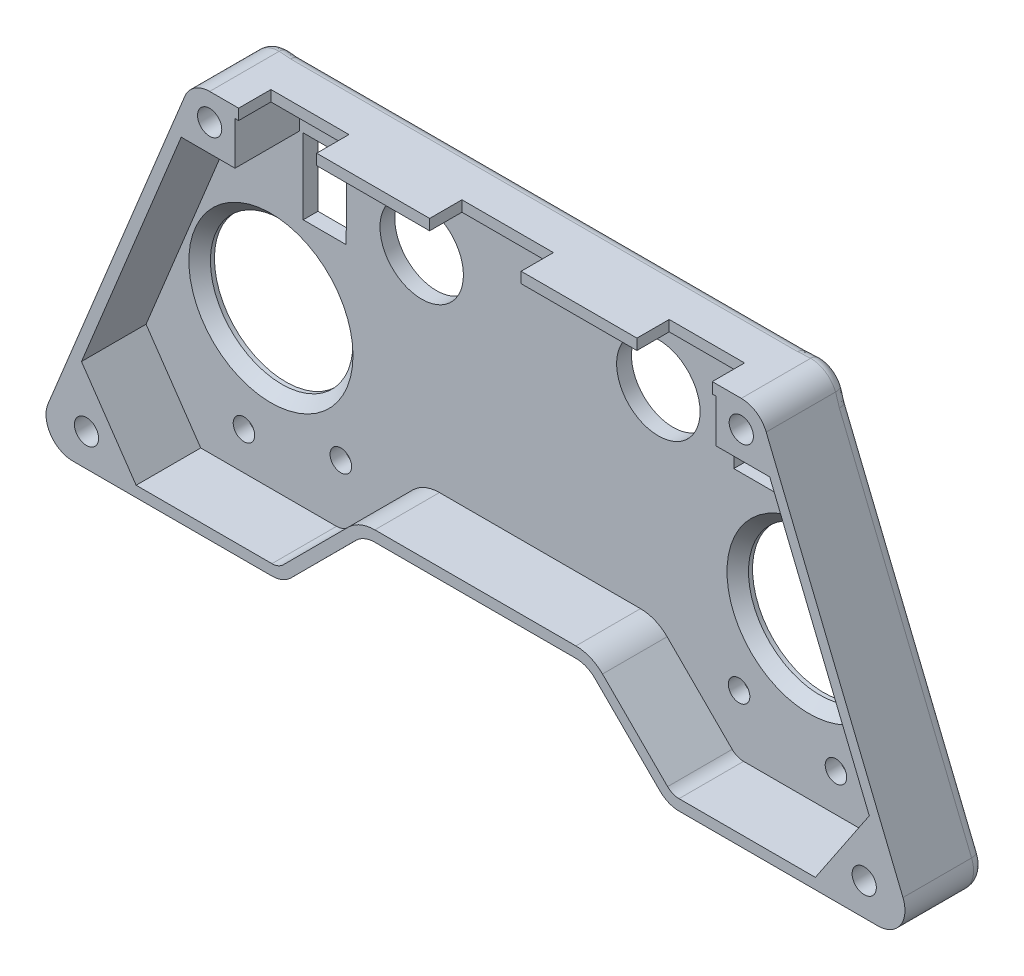
SolidWorks part; units mm, degrees
ref_plane "Plan de face" through (0, 0, 0) normal (0, 0, 1) x (1, 0, 0)
ref_plane "Plan de dessus" through (0, 0, 0) normal (0, 1, 0) x (1, 0, 0)
ref_plane "Plan de droite" through (0, 0, 0) normal (1, 0, 0) x (0, 0, -1)
sketch "Esquisse1" plane through (0, 0, 0) normal (0, 0, 1) x (1, 0, 0)
  line L8 (18.6789, 0) -> (-18.6789, 0)
  line L9 (-22.2167, -1.4667) -> (-34.2683, -13.5333)
  line L10 (-37.806, -15) -> (-74.7892, -15)
  line L11 (22.2123, -1.4623) -> (34.3028, -13.5377)
  line L12 (37.8361, -15) -> (74.8229, -15)
  line L13 (-79.4178, -8.109) -> (-54.0033, 54.0973)
  line L14 (-49.3747, 57.2063) -> (49.4084, 57.2063)
  line L15 (54.037, 54.0973) -> (79.4515, -8.109)
  line L16 (0.0169, 57.2063) -> (0, 0) construction
  arc A0 (-34.2683, -13.5333) -> (-37.806, -15) centre (-37.806, -10) cw
  arc A1 (-18.6789, 0) -> (-22.2167, -1.4667) centre (-18.6789, -5) ccw
  arc A2 (22.2123, -1.4623) -> (18.6789, 0) centre (18.6789, -5) ccw
  arc A3 (37.8361, -15) -> (34.3028, -13.5377) centre (37.8361, -10) cw
  arc A4 (54.037, 54.0973) -> (49.4084, 57.2063) centre (49.4084, 52.2063) ccw
  arc A5 (-49.3747, 57.2063) -> (-54.0033, 54.0973) centre (-49.3747, 52.2063) ccw
  arc A6 (79.4515, -8.109) -> (74.8229, -15) centre (74.8229, -10) cw
  arc A7 (-79.4178, -8.109) -> (-74.7892, -15) centre (-74.7892, -10) ccw
  point P4 (0, 0)
  point P12 (-35.7331, -15)
  point P15 (-20.7518, 0)
  point P18 (20.7482, 0)
  point P21 (35.7669, -15)
  point P24 (52.7669, 57.2063)
  point P27 (-52.7331, 57.2063)
  point P30 (82.2669, -15)
  point P33 (-82.2331, -15)
  dimension "D10" = 5
  dimension "D1" = 46.5
  dimension "D2" = 46.5
  dimension "D3" = 41.5
  dimension "D4" = 15
  dimension "D5" = 15
  dimension "D6" = 21.2
  dimension "D7" = 78
  dimension "D8" = 78
  dimension "D9" = 105.5
extrude "Boss.-Extru.1" add sketch "Esquisse1" along normal blind 14.75
sketch "Sketch1" plane through (0, 0, 0) normal (0, 0, 1) x (1, 0, 0)
  line L0 (37.8361, -15) -> (74.8229, -15) construction
  line L1 (49.4084, 57.2063) -> (-49.3747, 57.2063) construction
  line L2 (44.0169, 47.2063) -> (36.0169, 47.2063)
  line L3 (44.0169, 47.2063) -> (44.0169, 33.2063)
  line L4 (44.0169, 33.2063) -> (36.0169, 33.2063)
  line L5 (36.0169, 47.2063) -> (36.0169, 33.2063)
  line L6 (0.0169, 57.2063) -> (0, 0) construction
  line L7 (-18.6789, 0) -> (18.6789, 0) construction
  line L8 (-43.9973, 33.2322) -> (-35.9973, 33.2275)
  line L9 (-35.989, 47.2275) -> (-35.9973, 33.2275)
  line L10 (-43.989, 47.2322) -> (-35.989, 47.2275)
  line L11 (-43.989, 47.2322) -> (-43.9973, 33.2322)
  circle A0 centre (50, 16) radius 13.25
  circle A1 centre (22, 39.2063) radius 7.75
  circle A2 centre (-49.9906, 16.0295) radius 13.25
  circle A3 centre (-21.9769, 39.2193) radius 7.75
  point P11 (0.0169, 57.2063)
  dimension "D1" = 26.5
  dimension "D2" = 31
  dimension "D3" = 50
  dimension "D7" = 15.5
  dimension "D8" = 22
  dimension "D10" = 18
  dimension "D4" = 8
  dimension "D5" = 14
  dimension "D6" = 36
  dimension "D9" = 10
extrude "Cut-Extrude4" cut sketch "Sketch1" along normal blind 40 contours A0 | L3 L2 L5 L4 | A1 | A3 | L8 L9 L10 L11 | A2
sketch "Sketch3" plane through (0, 0, 14.75) normal (0, 0, 1) x (1, 0, 0)
  line L0 (-54.6596, 47.2027) -> (-73.1968, 1.8299)
  line L1 (44.6919, 55.2063) -> (-44.6596, 55.2063)
  line L2 (54.6919, 47.2063) -> (73.1932, 1.9213)
  line L3 (49.4084, 57.2063) -> (-49.3747, 57.2063) construction
  line L7 (-54.0033, 54.0973) -> (-79.4178, -8.109) construction
  line L8 (79.4515, -8.109) -> (54.037, 54.0973) construction
  line L72 (-73.1968, 1.8299) -> (-63.0357, -13)
  line L74 (-37.806, -13) -> (-63.0357, -13)
  line L75 (63.1707, -13) -> (73.1932, 1.9213)
  line L76 (37.8361, -13) -> (63.1707, -13)
  line L78 (-54.6596, 47.2027) -> (-44.6596, 47.2027)
  line L79 (-44.6596, 47.2027) -> (-44.6596, 55.2063)
  line L80 (77.6001, -8.8654) -> (52.1856, 53.3409)
  line L81 (37.8361, -13) -> (74.8229, -13)
  line L82 (23.6256, -0.0472) -> (35.7161, -12.1226)
  line L83 (-18.6789, 2) -> (18.6789, 2)
  line L84 (-35.6834, -12.12) -> (-23.6318, -0.0533)
  line L85 (-74.7892, -13) -> (-37.806, -13)
  line L86 (-52.1519, 53.3409) -> (-77.5664, -8.8654)
  line L87 (49.4084, 55.2063) -> (-49.3747, 55.2063)
  line L90 (23.6256, -0.0472) -> (35.7161, -12.1226)
  line L91 (-18.6789, 2) -> (18.6789, 2)
  line L92 (-35.6834, -12.12) -> (-23.6318, -0.0533)
  line L96 (44.6919, 55.2063) -> (44.6919, 47.2063)
  line L97 (44.6919, 47.2063) -> (54.6919, 47.2063)
  arc A0 (-79.4178, -8.109) -> (-74.7892, -15) centre (-74.7892, -10) ccw construction
  arc A1 (74.8229, -15) -> (79.4515, -8.109) centre (74.8229, -10) ccw construction
  arc A72 (52.1856, 53.3409) -> (49.4084, 55.2063) centre (49.4084, 52.2063) ccw
  arc A73 (74.8229, -13) -> (77.6001, -8.8654) centre (74.8229, -10) ccw
  arc A74 (35.7161, -12.1226) -> (37.8361, -13) centre (37.8361, -10) ccw
  arc A75 (23.6256, -0.0472) -> (18.6789, 2) centre (18.6789, -5) ccw
  arc A76 (-18.6789, 2) -> (-23.6318, -0.0533) centre (-18.6789, -5) ccw
  arc A77 (-37.806, -13) -> (-35.6834, -12.12) centre (-37.806, -10) ccw
  arc A78 (-77.5664, -8.8654) -> (-74.7892, -13) centre (-74.7892, -10) ccw
  arc A79 (-49.3747, 55.2063) -> (-52.1519, 53.3409) centre (-49.3747, 52.2063) ccw
  arc A82 (35.7161, -12.1226) -> (37.8361, -13) centre (37.8361, -10) ccw
  arc A83 (23.6256, -0.0472) -> (18.6789, 2) centre (18.6789, -5) ccw
  arc A84 (-18.6789, 2) -> (-23.6318, -0.0533) centre (-18.6789, -5) ccw
  arc A85 (-37.806, -13) -> (-35.6834, -12.12) centre (-37.806, -10) ccw
  point P19 (-78.9398, -12.7879)
  point P23 (78.9735, -12.7879)
  dimension "D2" = 2
  dimension "D3" = 2
  dimension "D4" = 10
  dimension "D5" = 8.0036
  dimension "D6" = 2
  dimension "D7" = 2
  dimension "D8" = 10
  dimension "D9" = 8
  dimension "D10" = 13
  dimension "D11" = 13
  dimension "D12" = 2
  dimension "D1" = 2
extrude "Cut-Extrude5" cut sketch "Sketch3" against normal blind 12
chamfer "Chamfer1" distance 2 angle 45 2 edges at (-36.7406, 16.0295, 2.75) (63.25, 16, 2.75)
sketch "Sketch4" plane through (0, 0, 14.75) normal (0, 0, 1) x (1, 0, 0)
  line L7 (-8.5, 61.4028) -> (8.5, 61.4028)
  line L8 (-8.5, 61.4028) -> (-8.5, 49.3129)
  line L9 (-8.5, 49.3129) -> (8.5, 49.3129)
  line L10 (8.5, 61.4028) -> (8.5, 49.3129)
  line L11 (30.0169, 61.4028) -> (44.0169, 61.4028)
  line L12 (30.0169, 61.4028) -> (30.0169, 49.3129)
  line L13 (30.0169, 49.3129) -> (44.0169, 49.3129)
  line L14 (44.0169, 61.4028) -> (44.0169, 49.3129)
  line L16 (-43.9932, 60.0939) -> (-29.4932, 60.0939)
  line L17 (-43.9932, 60.0939) -> (-43.9932, 51.868)
  line L18 (-43.9932, 51.868) -> (-29.4932, 51.868)
  line L19 (-29.4932, 60.0939) -> (-29.4932, 51.868)
  dimension "D1" = 17
  dimension "D2" = 8.5
  dimension "D3" = 14
  dimension "D4" = 14.5
extrude "Cut-Extrude6" cut sketch "Sketch4" against normal blind 6
sketch "Sketch6" plane through (0, 0, 0) normal (0, 0, -1) x (-1, 0, 0)
  line L1 (-49.4084, 57.2063) -> (49.3747, 57.2063) construction
  line L2 (-79.4515, -8.109) -> (-54.037, 54.0973) construction
  line L3 (-37.8361, -15) -> (-74.8229, -15) construction
  line L4 (0, 0) -> (-0.0169, 57.2063) construction
  circle A0 centre (-49.4084, 52.2063) radius 2.25
  circle A1 centre (-72.2539, -9) radius 2.25
  circle A2 centre (72.2592, -8.9574) radius 2.25
  circle A3 centre (49.3776, 52.2354) radius 2.25
  dimension "D1" = 4.5
  dimension "D2" = 5
  dimension "D3" = 5
  dimension "D4" = 6
  dimension "D5" = 7
  dimension "D6" = 4.5
extrude "Cut-Extrude7" cut sketch "Sketch6" against normal through all
sketch "Sketch7" plane through (0, 0, 0) normal (0, 0, -1) x (-1, 0, 0)
  circle A0 centre (-49.4084, 52.2063) radius 3.75
  circle A1 centre (49.3776, 52.2354) radius 3.75
  circle A2 centre (72.2592, -8.9574) radius 3.75
  circle A3 centre (-72.2539, -9) radius 3.75
  dimension "D1" = 7.5
  dimension "D2" = 7.5
  dimension "D3" = 7.5
  dimension "D4" = 7.5
extrude "Cut-Extrude8" cut sketch "Sketch7" against normal blind 7
sketch "Sketch8" plane through (0, 0, 0) normal (0, 0, -1) x (-1, 0, 0)
  line L0 (-37.8361, -15) -> (-74.8229, -15) construction
  line L1 (0, 0) -> (-0.0169, 57.2063) construction
  line L2 (18.6789, 0) -> (-18.6789, 0) construction
  line L3 (-49.4084, 57.2063) -> (49.3747, 57.2063) construction
  circle A0 centre (-55, -6) radius 2
  circle A1 centre (-37, -2) radius 2
  circle A2 centre (55.0035, -5.9676) radius 2
  circle A3 centre (37.0012, -1.9782) radius 2
  dimension "D1" = 9
  dimension "D2" = 13
  dimension "D3" = 4
  dimension "D4" = 4
  dimension "D5" = 37
  dimension "D6" = 55
extrude "Cut-Extrude9" cut sketch "Sketch8" against normal through all
fillet "Fillet1" radius 2 14 edges at (56.3295, -15, 0) (35.9241, -14.62, 0) (28.2575, -7.5, 0) (20.5909, -0.38, 0) (0, 0, 0) (-20.5938, -0.3812, 0) (-28.2425, -7.5, 0) (-35.8912, -14.6188, 0) (-56.2976, -15, 0) (-66.7106, 22.9942, 0) (0.0169, 57.2063, 0) (66.7443, 22.9942, 0) (78.9735, -12.7879, 0) (-78.9398, -12.7879, 0)
